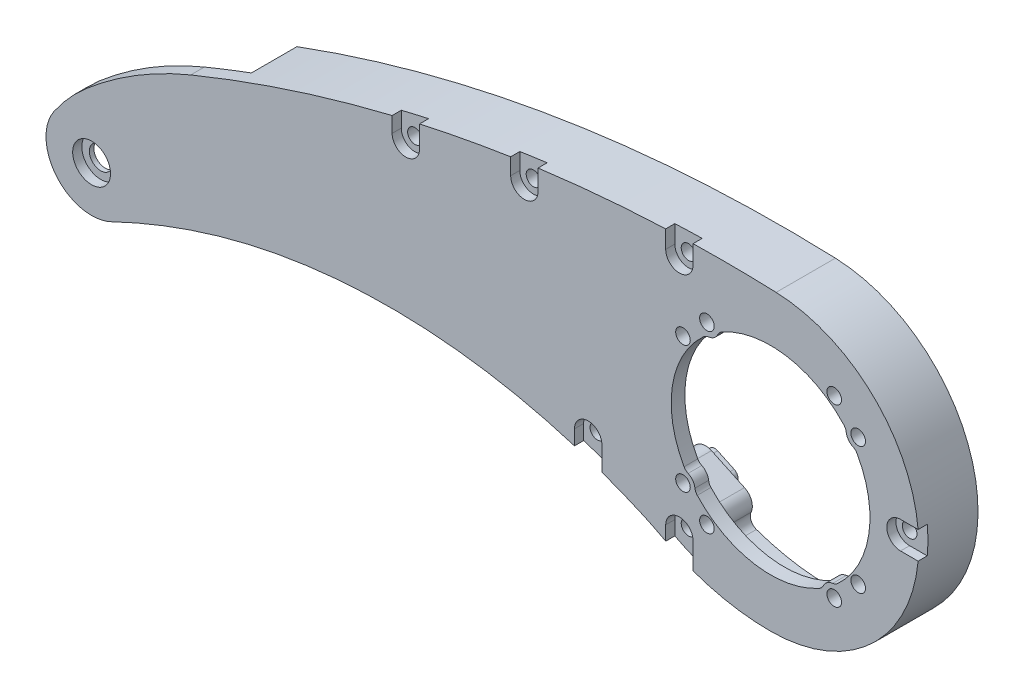
SolidWorks part; units mm, degrees
material "6061-T6 (SS)"
ref_plane "前视基准面" through (0, 0, 0) normal (0, 0, 1) x (1, 0, 0)
ref_plane "上视基准面" through (0, 0, 0) normal (0, 1, 0) x (1, 0, 0)
ref_plane "右视基准面" through (0, 0, 0) normal (1, 0, 0) x (0, 0, -1)
other "Configuration Table"
sketch "草图1" plane through (0, 0, 0) normal (0, 0, 1) x (1, 0, 0)
  line L0 (-74.3846, 0) -> (17.4339, 0) construction
  line L1 (0, 31.8895) -> (0, -25.7876) construction
  line L2 (0, 0) -> (19.2142, 13.9599) construction
  line L3 (0, 0) -> (13.9599, 19.2142) construction
  line L4 (0, 0) -> (-148.9161, -18) construction
  line L6 (0, 0) -> (-1.2281, 22.9672) construction
  line L8 (-1.2281, 22.9672) -> (-150.1441, 4.9672) construction
  line L9 (-150.1441, 4.9672) -> (-148.9161, -18) construction
  line L10 (-148.9161, -18) -> (-97.5528, -158.9319)
  line L12 (0, 0) -> (-103.1063, -167.9797) construction
  arc A116 (16.0762, 14.724) -> (-10.7394, 18.9712) centre (0, 0) ccw
  circle A117 centre (0, 0) radius 23.75 construction
  circle A118 centre (19.2142, 13.9599) radius 1.6
  circle A119 centre (13.9599, 19.2142) radius 1.6
  circle A120 centre (19.2142, -13.9599) radius 1.6
  circle A121 centre (13.9599, -19.2142) radius 1.6
  circle A122 centre (-13.9599, -19.2142) radius 1.6
  circle A123 centre (-19.2142, -13.9599) radius 1.6
  circle A124 centre (-19.2142, 13.9599) radius 1.6
  circle A125 centre (-13.9599, 19.2142) radius 1.6
  arc A126 (0, -32.5) -> (1.2171, 32.4772) centre (0, 0) ccw
  arc A127 (-157.1671, -12.3502) -> (-144.5702, -27.0063) centre (-148.9161, -18) ccw
  arc A134 (-28.3708, -24.2609) -> (-127.3793, -19.9637) centre (-83.3912, -149.2082) ccw
  arc A135 (-127.3793, -19.9637) -> (-144.5702, -27.0063) centre (-78.0965, -164.7651) ccw
  arc A136 (1.2171, 32.4772) -> (-127.1723, 9.5805) centre (-10.2849, -274.4361) ccw
  arc A138 (-23.6381, -26.5665) -> (-28.3708, -24.2609) centre (-55.9067, -86.7929) ccw
  arc A139 (0, -32.5) -> (-23.6381, -26.5665) centre (0, 17.5518) cw
  arc A140 (16.5853, 13.6255) -> (18.0838, 11.5631) centre (19.2142, 13.9599) ccw
  arc A141 (16.5853, 13.6255) -> (16.0762, 14.724) centre (14.6013, 13.3732) ccw
  arc A142 (18.0838, 11.5631) -> (18.9712, 10.7394) centre (17.2307, 9.7541) cw
  arc A143 (11.5631, -18.0838) -> (10.7394, -18.9712) centre (9.7541, -17.2307) cw
  arc A144 (13.6255, -16.5853) -> (11.5631, -18.0838) centre (13.9599, -19.2142) ccw
  arc A145 (13.6255, -16.5853) -> (14.724, -16.0762) centre (13.3732, -14.6013) ccw
  arc A146 (-18.0838, -11.5631) -> (-18.9712, -10.7394) centre (-17.2307, -9.7541) cw
  arc A147 (-16.5853, -13.6255) -> (-18.0838, -11.5631) centre (-19.2142, -13.9599) ccw
  arc A148 (-16.5853, -13.6255) -> (-16.0762, -14.724) centre (-14.6013, -13.3732) ccw
  arc A149 (-11.5631, 18.0838) -> (-10.7394, 18.9712) centre (-9.7541, 17.2307) cw
  arc A150 (-13.6255, 16.5853) -> (-11.5631, 18.0838) centre (-13.9599, 19.2142) ccw
  arc A151 (-13.6255, 16.5853) -> (-14.724, 16.0762) centre (-13.3732, 14.6013) ccw
  arc A152 (-16.0762, -14.724) -> (10.7394, -18.9712) centre (0, 0) ccw
  arc A153 (14.724, -16.0762) -> (18.9712, 10.7394) centre (0, 0) ccw
  arc A154 (-14.724, 16.0762) -> (-18.9712, -10.7394) centre (0, 0) ccw
  arc A155 (-127.1723, 9.5805) -> (-150.1438, -4.5112) centre (-94.9478, -68.7195) ccw
  arc A156 (-150.1438, -4.5112) -> (-157.1671, -12.3502) centre (-123.7132, -35.2574) ccw
  arc A157 (11.5631, 18.0838) -> (10.7394, 18.9712) centre (9.7541, 17.2307) ccw
  arc A158 (11.5631, 18.0838) -> (13.6255, 16.5853) centre (13.9599, 19.2142) ccw
  arc A159 (13.6255, 16.5853) -> (14.724, 16.0762) centre (13.3732, 14.6013) cw
  arc A160 (16.5853, -13.6255) -> (16.0762, -14.724) centre (14.6013, -13.3732) cw
  arc A161 (18.0838, -11.5631) -> (16.5853, -13.6255) centre (19.2142, -13.9599) ccw
  arc A162 (18.0838, -11.5631) -> (18.9712, -10.7394) centre (17.2307, -9.7541) ccw
  arc A163 (-13.6255, -16.5853) -> (-14.724, -16.0762) centre (-13.3732, -14.6013) cw
  arc A164 (-11.5631, -18.0838) -> (-13.6255, -16.5853) centre (-13.9599, -19.2142) ccw
  arc A165 (-11.5631, -18.0838) -> (-10.7394, -18.9712) centre (-9.7541, -17.2307) ccw
  arc A166 (-16.5853, 13.6255) -> (-16.0762, 14.724) centre (-14.6013, 13.3732) cw
  arc A167 (-18.0838, 11.5631) -> (-16.5853, 13.6255) centre (-19.2142, 13.9599) ccw
  arc A168 (-18.0838, 11.5631) -> (-18.9712, 10.7394) centre (-17.2307, 9.7541) ccw
  arc A169 (18.9712, 10.7394) -> (16.0762, 14.724) centre (0, 0) ccw
  arc A170 (-10.7394, 18.9712) -> (-14.724, 16.0762) centre (0, 0) ccw
  arc A171 (10.7394, -18.9712) -> (14.724, -16.0762) centre (0, 0) ccw
  point P27 (0, 0)
  point P73 (0, 0)
  point P83 (0, 0)
  point P105 (0, 0)
  dimension "D1" = 43.6
  dimension "D3" = 36
  dimension "D4" = 3.2
  dimension "D2" = 47.5
  dimension "D6" = 3.2
  dimension "D8" = 65
  dimension "D15" = 20
  dimension "D16" = 5.3
  dimension "D17" = 2
  dimension "D5" = 18
  dimension "D9" = 18
  dimension "D10" = 150
  dimension "D11" = 23
  dimension "D12" = 150
  dimension "D13" = 103.132
  dimension "D14" = 51.566
  dimension "D19" = 2
  dimension "D7" = 4
  dimension "D18" = 4
  dimension "D20" = 4
extrude "凸台-拉伸1" add sketch "草图1" along normal blind 3 contours A135 A134 A138 A126 A127 A125 A124 A123 A122 A121 A120 A119 A118 A116 | A149 A170 A151 A150 | A142 A169 A141 A140 | A143 A171 A145 A144 region at (17.4035, 12.6444, 0) region at (-12.6444, 17.4035, 0) region at (12.6444, -17.4035, 0) region at (-60.0693, 1.6089, 0)
sketch "草图2" plane through (0, 0, 0) normal (0, 0, -1) x (-1, 0, 0)
  line L0 (-28.5, 0) -> (0, 0) construction
  line L2 (0, 0) -> (18.5599, 13.5842) construction
  line L3 (18.5599, 13.5842) -> (167.476, -4.4158) construction
  line L4 (167.476, -4.4158) -> (148.9161, -18) construction
  line L5 (148.9161, -18) -> (10.6983, -76.2738) construction
  line L7 (25.351, 15.2815) -> (162.3611, -1.2794) construction
  line L9 (24.751, 10.3176) -> (161.7611, -6.2433) construction
  line L11 (19.8643, 25.54) -> (27.8561, 25.1781)
  line L13 (18.7235, -21.0787) -> (25.9631, -17.6745)
  line L16 (53.5282, 22.5613) -> (61.4287, 21.3032)
  line L17 (79.2716, 17.6568) -> (87.0322, 15.7143)
  line L19 (116.7753, -9.6208) -> (124.5035, -11.6883)
  line L20 (39.1553, -12.6715) -> (46.8316, -10.4188)
  arc A111 (-1.1422, 30.4786) -> (-30.0624, 5.1483) centre (0, 0) ccw
  arc A112 (0, -30.5) -> (16.1065, -27.7202) centre (0, 17.5518) ccw
  arc A114 (110.6875, -13.3991) -> (53.0075, -14.0564) centre (83.3912, -149.2082) ccw
  arc A115 (128.6525, -18.2859) -> (127.8763, -18.0203) centre (78.0965, -164.7651) ccw
  arc A116 (144.5702, -27.0063) -> (157.1671, -12.3502) centre (148.9161, -18) ccw
  arc A118 (157.1671, -12.3502) -> (150.1438, -4.5112) centre (123.7132, -35.2574) ccw
  arc A119 (127.1723, 9.5805) -> (-1.2171, 32.4772) centre (10.2849, -274.4361) ccw
  arc A120 (-1.2171, 32.4772) -> (0, -32.5) centre (0, 0) ccw
  arc A121 (-1.0673, 28.48) -> (0, -28.5) centre (0, 0) ccw construction
  arc A122 (0, -32.5) -> (23.6381, -26.5665) centre (0, 17.5518) ccw
  arc A123 (28.3708, -24.2609) -> (23.6381, -26.5665) centre (55.9067, -86.7929) ccw
  arc A124 (127.3793, -19.9637) -> (28.3708, -24.2609) centre (83.3912, -149.2082) ccw
  arc A125 (144.5702, -27.0063) -> (127.3793, -19.9637) centre (78.0965, -164.7651) ccw
  arc A126 (144.5702, -27.0063) -> (157.1671, -12.3502) centre (148.9161, -18) ccw
  arc A128 (127.1723, 9.5805) -> (-1.2171, 32.4772) centre (10.2849, -274.4361) ccw
  arc A129 (-1.2171, 32.4772) -> (0, -32.5) centre (0, 0) ccw
  arc A130 (0, -32.5) -> (23.6381, -26.5665) centre (0, 17.5518) ccw
  arc A131 (28.3708, -24.2609) -> (23.6381, -26.5665) centre (55.9067, -86.7929) ccw
  arc A132 (127.3793, -19.9637) -> (28.3708, -24.2609) centre (83.3912, -149.2082) ccw
  arc A133 (144.5702, -27.0063) -> (127.3793, -19.9637) centre (78.0965, -164.7651) ccw
  arc A134 (0, -28.5) -> (21.749, -23.0407) centre (0, 17.5518) ccw construction
  arc A135 (26.7587, -20.6001) -> (21.749, -23.0407) centre (55.9067, -86.7929) ccw construction
  arc A136 (128.6681, -16.177) -> (26.7587, -20.6001) centre (83.3912, -149.2082) ccw construction
  arc A137 (146.3086, -23.4038) -> (128.6681, -16.177) centre (78.0965, -164.7651) ccw construction
  arc A138 (146.3086, -23.4038) -> (153.7238, -14.4104) centre (148.9161, -18) ccw construction
  arc A139 (153.7238, -14.4104) -> (126.0955, 5.6977) centre (120.8678, -30.5198) ccw construction
  arc A140 (126.0955, 5.6977) -> (-1.0673, 28.48) centre (10.2849, -274.4361) ccw construction
  arc A141 (-28.3421, -2.9958) -> (-28.3421, 2.9958) centre (-28.5, 0) ccw
  arc A142 (-28.3421, 2.9958) -> (-30.0624, 5.1483) centre (-28.2451, 4.837) cw
  arc A143 (-28.3421, -2.9958) -> (-30.0624, -5.1483) centre (-28.2451, -4.837) ccw
  arc A144 (-30.0624, -5.1483) -> (0, -30.5) centre (0, 0) ccw
  circle A145 centre (-28.5, 0) radius 1.6
  arc A146 (-1.1422, 30.4786) -> (0, -30.5) centre (0, 0) ccw construction
  circle A147 centre (18.5599, 13.5842) radius 7 construction
  circle A148 centre (167.476, -4.4158) radius 6 construction
  arc A149 (17.0011, 28.6182) -> (19.8643, 25.54) centre (20, 28.5369) ccw
  arc A150 (27.8561, 25.1781) -> (30.9858, 27.985) centre (27.9918, 28.175) ccw
  arc A151 (17.0011, 28.6182) -> (15.0491, 30.6555) centre (15.0181, 28.672) ccw
  arc A152 (30.9858, 27.985) -> (33.1139, 29.8374) centre (32.9655, 27.8593) cw
  arc A153 (15.0491, 30.6555) -> (-1.1422, 30.4786) centre (10.2849, -274.4361) ccw
  circle A154 centre (20, 28.5369) radius 1.6
  arc A155 (126.6313, 7.6402) -> (-1.1422, 30.4786) centre (10.2849, -274.4361) ccw construction
  arc A156 (17.2617, -25.019) -> (18.7235, -21.0787) centre (20, -23.7935) cw
  arc A157 (25.9631, -17.6745) -> (30.0023, -19.2201) centre (27.2396, -20.3894) cw
  circle A158 centre (20, -23.7935) radius 1.6
  arc A159 (17.2617, -25.019) -> (16.1065, -27.7202) centre (15.4362, -25.8359) cw
  arc A160 (30.0023, -19.2201) -> (32.6241, -20.3211) centre (31.8778, -18.4263) ccw
  circle A161 centre (54, 25.524) radius 1.6
  arc A162 (27.5648, -22.4305) -> (22.6935, -24.8036) centre (55.9067, -86.7929) ccw construction
  arc A163 (0, -30.5) -> (22.6935, -24.8036) centre (0, 17.5518) ccw construction
  arc A164 (128.0237, -18.0703) -> (27.5648, -22.4305) centre (83.3912, -149.2082) ccw construction
  arc A165 (51.0293, 25.9419) -> (53.5282, 22.5613) centre (54, 25.524) ccw
  arc A166 (61.4287, 21.3032) -> (64.8541, 23.7404) centre (61.9005, 24.2659) ccw
  arc A167 (51.0293, 25.9419) -> (49.3187, 28.1856) centre (49.0649, 26.2183) ccw
  arc A168 (64.8541, 23.7404) -> (67.177, 25.3419) centre (66.8071, 23.393) cw
  arc A169 (49.3187, 28.1856) -> (33.1139, 29.8374) centre (10.2849, -274.4361) ccw
  circle A170 centre (80, 20.567) radius 1.6
  arc A171 (77.077, 21.2425) -> (79.2716, 17.6568) centre (80, 20.567) ccw
  arc A172 (87.0322, 15.7143) -> (90.6571, 17.8435) centre (87.7606, 18.6246) ccw
  arc A173 (77.077, 21.2425) -> (75.5687, 23.6269) centre (75.1443, 21.6892) ccw
  arc A175 (75.5687, 23.6269) -> (67.177, 25.3419) centre (10.2849, -274.4361) ccw
  circle A176 centre (40, -15.5501) radius 1.6
  circle A177 centre (116, -12.5189) radius 1.6
  arc A178 (37.1566, -16.5068) -> (39.1553, -12.6715) centre (40, -15.5501) cw
  arc A180 (37.1566, -16.5068) -> (35.9243, -19.0695) centre (35.2265, -17.1563) cw
  arc A182 (35.9243, -19.0695) -> (32.6241, -20.3211) centre (83.3912, -149.2082) ccw
  arc A183 (113.0746, -11.854) -> (116.7753, -9.6208) centre (116, -12.5189) cw
  arc A184 (124.5035, -11.6883) -> (126.5902, -15.4859) centre (123.7282, -14.5864) cw
  arc A185 (113.0746, -11.854) -> (110.6875, -13.3991) centre (111.0888, -11.4026) cw
  arc A186 (126.5902, -15.4859) -> (127.8763, -18.0203) centre (128.5292, -16.0954) ccw
  arc A187 (128.6525, -18.2859) -> (129.8863, -20.8413) centre (128, -20.1764) cw
  arc A188 (145.4394, -25.205) -> (128.0237, -18.0703) centre (78.0965, -164.7651) ccw construction
  arc A189 (144.5702, -27.0063) -> (127.3793, -19.9637) centre (78.0965, -164.7651) ccw construction
  arc A190 (145.4394, -25.205) -> (155.4422, -13.3729) centre (148.9161, -18) ccw construction
  arc A191 (75.5687, 23.6269) -> (93.1109, 19.2362) centre (10.2849, -274.4361) cw construction
  arc A192 (90.6571, 17.8435) -> (93.1109, 19.2362) centre (92.5724, 17.327) cw
  arc A193 (155.4422, -13.3729) -> (126.6313, 7.6402) centre (120.8678, -30.5198) ccw construction
  arc A194 (15.0491, 30.6555) -> (33.1139, 29.8374) centre (10.2849, -274.4361) cw construction
  arc A195 (49.3187, 28.1856) -> (67.177, 25.3419) centre (10.2849, -274.4361) cw construction
  arc A196 (93.1109, 19.2362) -> (114.3181, 12.4099) centre (10.2849, -274.4361) cw
  arc A197 (114.3181, 12.4099) -> (116.8779, 13.6021) centre (115, 14.2901) ccw
  arc A198 (46.8316, -10.4188) -> (50.5858, -12.566) centre (47.6763, -13.2974) cw
  arc A199 (50.5858, -12.566) -> (53.0075, -14.0564) centre (52.5608, -12.0695) ccw
  arc A200 (54.5841, -13.7116) -> (56.9593, -15.2663) centre (55, -15.6678) cw
  arc A207 (157.1671, -12.3502) -> (127.1723, 9.5805) centre (120.8678, -30.5198) ccw construction
  arc A208 (157.1671, -12.3502) -> (150.1438, -4.5112) centre (123.7132, -35.2574) ccw
  arc A209 (150.1438, -4.5112) -> (127.1723, 9.5805) centre (94.9478, -68.7195) ccw
  arc A210 (150.1438, -4.5112) -> (127.1723, 9.5805) centre (94.9478, -68.7195) ccw
  point P113 (16.5105, -418.9921)
  arc M20 (127.1723, 9.5805) -> (-1.2171, 32.4772) centre (10.2849, -274.4361) ccw
  arc M21 (-1.2171, 32.4772) -> (0, -32.5) centre (0, 0) ccw
  arc M22 (0, -32.5) -> (23.6381, -26.5665) centre (0, 17.5518) ccw
  arc M23 (23.6381, -26.5665) -> (28.3708, -24.2609) centre (55.9067, -86.7929) cw
  arc M24 (28.3708, -24.2609) -> (127.3793, -19.9637) centre (83.3912, -149.2082) cw
  arc M25 (127.3793, -19.9637) -> (144.5702, -27.0063) centre (78.0965, -164.7651) cw
  dimension "D7" = 150
  dimension "D9" = 14
  dimension "D11" = 12
  dimension "D12" = 150
  dimension "D13" = 8
  dimension "D10" = 2.5
  dimension "D8" = 166.66
  dimension "D14" = 20
  dimension "D15" = 8
  dimension "D16" = 8
  dimension "D17" = 8
  dimension "D18" = 54
  dimension "D19" = 80
  dimension "D20" = 8
  dimension "D21" = 40
  dimension "D22" = 116
  dimension "D23" = 8
  dimension "D6" = 23
  dimension "D25" = 128
  dimension "D26" = 2
  dimension "D27" = 115
  dimension "D28" = 20
  dimension "D4" = 6
  dimension "D5" = 3.2
  dimension "D24" = 2
  dimension "D29" = 2
  dimension "D1" = 0
  dimension "D2" = 2
  dimension "D3" = 2
  dimension "D30" = 55
extrude "凸台-拉伸2" add sketch "草图2" along normal blind 10 contours M20 M21 M22 M23 M24 M25 region at (-17.9227, 26.6047, 0)
sketch "草图4" plane through (0, 0, -10) normal (0, 0, -1) x (-1, 0, 0)
  line L0 (20, 28.5369) -> (27.9918, 28.175) construction
  line L3 (61.9005, 24.2659) -> (54, 25.524) construction
  line L8 (80, 20.567) -> (87.7606, 18.6246) construction
  line L9 (20, -23.7935) -> (27.2396, -20.3894) construction
  line L10 (40, -15.5501) -> (47.6763, -13.2974) construction
  line L11 (116, -12.5189) -> (123.7282, -14.5864) construction
  line L12 (27.2396, -20.3894) -> (23.6198, -22.0915) construction
  line L15 (27.8779, -21.7468) -> (24.2581, -23.4489)
  line L24 (26.6013, -19.032) -> (22.9815, -20.734)
  line L27 (27.9918, 28.175) -> (23.9959, 28.356) construction
  line L30 (27.924, 26.6766) -> (23.9281, 26.8575)
  line L33 (28.0597, 29.6735) -> (24.0638, 29.8545)
  line L36 (61.9005, 24.2659) -> (57.9502, 24.8949) construction
  line L39 (87.7606, 18.6246) -> (83.8803, 19.5958) construction
  line L40 (87.3964, 17.1695) -> (83.5161, 18.1407)
  line L41 (88.1248, 20.0797) -> (84.2445, 21.0509)
  line L42 (123.7282, -14.5864) -> (119.8641, -13.5526) construction
  line L43 (123.3406, -16.0354) -> (119.4765, -15.0017)
  line L44 (124.1159, -13.1373) -> (120.2518, -12.1036)
  line L45 (47.6763, -13.2974) -> (43.8382, -14.4238) construction
  line L46 (48.0987, -14.7367) -> (44.2605, -15.8631)
  line L47 (47.2539, -11.8581) -> (43.4158, -12.9845)
  line L48 (61.6646, 22.7845) -> (57.7143, 23.4136)
  line L49 (62.1363, 25.7472) -> (58.1861, 26.3763)
  arc A24 (27.8779, -21.7468) -> (26.6013, -19.032) centre (27.2396, -20.3894) ccw
  arc A25 (22.9815, -20.734) -> (24.2581, -23.4489) centre (23.6198, -22.0915) ccw
  arc A26 (27.924, 26.6766) -> (28.0597, 29.6735) centre (27.9918, 28.175) ccw
  arc A27 (24.0638, 29.8545) -> (23.9281, 26.8575) centre (23.9959, 28.356) ccw
  arc A30 (87.3964, 17.1695) -> (88.1248, 20.0797) centre (87.7606, 18.6246) ccw
  arc A31 (84.2445, 21.0509) -> (83.5161, 18.1407) centre (83.8803, 19.5958) ccw
  arc A32 (123.3406, -16.0354) -> (124.1159, -13.1373) centre (123.7282, -14.5864) ccw
  arc A33 (120.2518, -12.1036) -> (119.4765, -15.0017) centre (119.8641, -13.5526) ccw
  arc A34 (48.0987, -14.7367) -> (47.2539, -11.8581) centre (47.6763, -13.2974) ccw
  arc A35 (43.4158, -12.9845) -> (44.2605, -15.8631) centre (43.8382, -14.4238) ccw
  arc A36 (61.6646, 22.7845) -> (62.1363, 25.7472) centre (61.9005, 24.2659) ccw
  arc A37 (58.1861, 26.3763) -> (57.7143, 23.4136) centre (57.9502, 24.8949) ccw
  point P12 (25.4297, -21.2404)
  point P18 (25.9939, 28.2655)
  point P24 (59.9253, 24.5804)
  point P30 (85.8204, 19.1102)
  point P36 (121.7962, -14.0695)
  point P42 (45.7572, -13.8606)
  dimension "D2" = 1.5
  dimension "D1" = 4
extrude "凸台-拉伸3" add sketch "草图4" along normal blind 2 contours L33 A27 L30 A26 | L49 A37 L48 A36 | A30 L41 A31 L40 | A34 L47 A35 L46 | A24 L24 A25 L15
sketch "草图5" plane through (0, 0, -10) normal (0, 0, -1) x (-1, 0, 0)
  circle A2 centre (-28.5, 0) radius 1.6 construction
  circle A4 centre (-28.5, 0) radius 1.6
  circle A6 centre (54, 25.524) radius 1.6 construction
  circle A8 centre (80, 20.567) radius 1.6 construction
  circle A12 centre (40, -15.5501) radius 1.6 construction
  circle A14 centre (20, -23.7935) radius 1.6 construction
  circle A27 centre (20, 28.5369) radius 1.6 construction
  circle A28 centre (54, 25.524) radius 1.6
  circle A29 centre (80, 20.567) radius 1.6
  circle A31 centre (40, -15.5501) radius 1.6
  circle A32 centre (20, -23.7935) radius 1.6
  circle A33 centre (20, 28.5369) radius 1.6
extrude "切除-拉伸1" cut sketch "草图5" against normal up to next
sketch "草图10" plane through (0, 0, 0) normal (0, 0, -1) x (-1, 0, 0)
  circle A0 centre (148.9161, -18) radius 2.5
  dimension "D1" = 5
extrude "切除-拉伸4" cut sketch "草图10" against normal up to next
sketch "草图11" plane through (0, 0, 3) normal (0, 0, 1) x (1, 0, 0)
  circle A0 centre (-148.9161, -18) radius 4.15
  dimension "D1" = 8.3
extrude "切除-拉伸5" cut sketch "草图11" against normal blind 2
sketch "草图13" plane through (0, 0, 3) normal (0, 0, 1) x (1, 0, 0)
  line L0 (-83, 20.567) -> (-83, 23.9606)
  line L1 (-77, 20.567) -> (-77, 25.3591)
  line L2 (-57, 25.524) -> (-57, 29.1191)
  line L3 (-51, 25.524) -> (-51, 29.982)
  line L4 (-23, 28.5369) -> (-23, 32.4293)
  line L5 (-17, 28.5369) -> (-17, 32.6192)
  line L8 (-43, -15.5501) -> (-43, -18.7949)
  line L9 (-37, -15.5501) -> (-37, -20.8067)
  line L10 (-23, -23.7935) -> (-23, -26.9025)
  line L11 (-17, -23.7935) -> (-17, -29.5246)
  line L12 (28.5, 3) -> (32.3612, 3)
  line L13 (28.5, -3) -> (32.3612, -3)
  line L14 (28.5, 3) -> (28.5, -3) construction
  arc A0 (-83, 20.567) -> (-77, 20.567) centre (-80, 20.567) ccw
  arc A1 (-57, 25.524) -> (-51, 25.524) centre (-54, 25.524) ccw
  arc A2 (-23, 28.5369) -> (-17, 28.5369) centre (-20, 28.5369) ccw
  arc A3 (28.5, 3) -> (28.5, -3) centre (28.5, 0) ccw
  arc A5 (-37, -15.5501) -> (-43, -15.5501) centre (-40, -15.5501) ccw
  arc A7 (-23.6381, -26.5665) -> (0, -32.5) centre (0, 17.5518) ccw construction
  arc A8 (1.2171, 32.4772) -> (-127.1723, 9.5805) centre (-10.2849, -274.4361) ccw construction
  arc A9 (-28.3708, -24.2609) -> (-127.3793, -19.9637) centre (-83.3912, -149.2082) ccw construction
  arc A10 (-23.6381, -26.5665) -> (0, -32.5) centre (0, 17.5518) ccw
  arc A11 (-23.6381, -26.5665) -> (-28.3708, -24.2609) centre (-55.9067, -86.7929) ccw construction
  arc A12 (0, -32.5) -> (1.2171, 32.4772) centre (0, 0) ccw construction
  arc A13 (1.2171, 32.4772) -> (-127.1723, 9.5805) centre (-10.2849, -274.4361) ccw
  arc A15 (0, -32.5) -> (1.2171, 32.4772) centre (0, 0) ccw
  arc A16 (-23.6381, -26.5665) -> (-28.3708, -24.2609) centre (-55.9067, -86.7929) ccw
  arc A18 (-17, -23.7935) -> (-23, -23.7935) centre (-20, -23.7935) ccw
  arc A19 (-28.3708, -24.2609) -> (-127.3793, -19.9637) centre (-83.3912, -149.2082) ccw
  circle M9 centre (28.5, 0) radius 1.6
  circle M10 centre (-54, 25.524) radius 1.6
  circle M11 centre (-80, 20.567) radius 1.6
  circle M13 centre (-40, -15.5501) radius 1.6
  circle M14 centre (-20, -23.7935) radius 1.6
  circle M15 centre (-20, 28.5369) radius 1.6
  arc M17 (-127.3793, -19.9637) -> (-28.3708, -24.2609) centre (-83.3912, -149.2082) cw
  arc M19 (-23.6381, -26.5665) -> (0, -32.5) centre (0, 17.5518) ccw
  arc M20 (0, -32.5) -> (1.2171, 32.4772) centre (0, 0) ccw
  arc M21 (1.2171, 32.4772) -> (-127.1723, 9.5805) centre (-10.2849, -274.4361) ccw
  dimension "D1" = 6
  dimension "D2" = 6
  dimension "D3" = 3
extrude "切除-拉伸6" cut sketch "草图13" against normal blind 2 contours L9 A5 L8 M17 M13 | L11 A18 L10 M19 M14 | L12 L14 L13 M9 M20 | L14 A3 M9 | L4 A2 L5 M21 M15 | L2 A1 L3 M21 M10 | L0 A0 L1 M21 M11 region at (-39.9559, -19.6692, 3) region at (-20.0005, -28.2147, 3) region at (30.7421, 0, 3) region at (-19.9975, 32.4462, 3) region at (-53.9885, 29.4706, 3) region at (-82.9017, 22.2638, 3) region at (28.4329, 2.3, 3)
sketch "草图14" plane through (0, 0, 0) normal (0, 0, -1) x (-1, 0, 0)
  circle A0 centre (148.9161, -18) radius 10
  circle A1 centre (148.9161, -18) radius 7
  dimension "D1" = 14
  dimension "D2" = 20
extrude "凸台-拉伸4" add sketch "草图14" along normal blind 1.5
